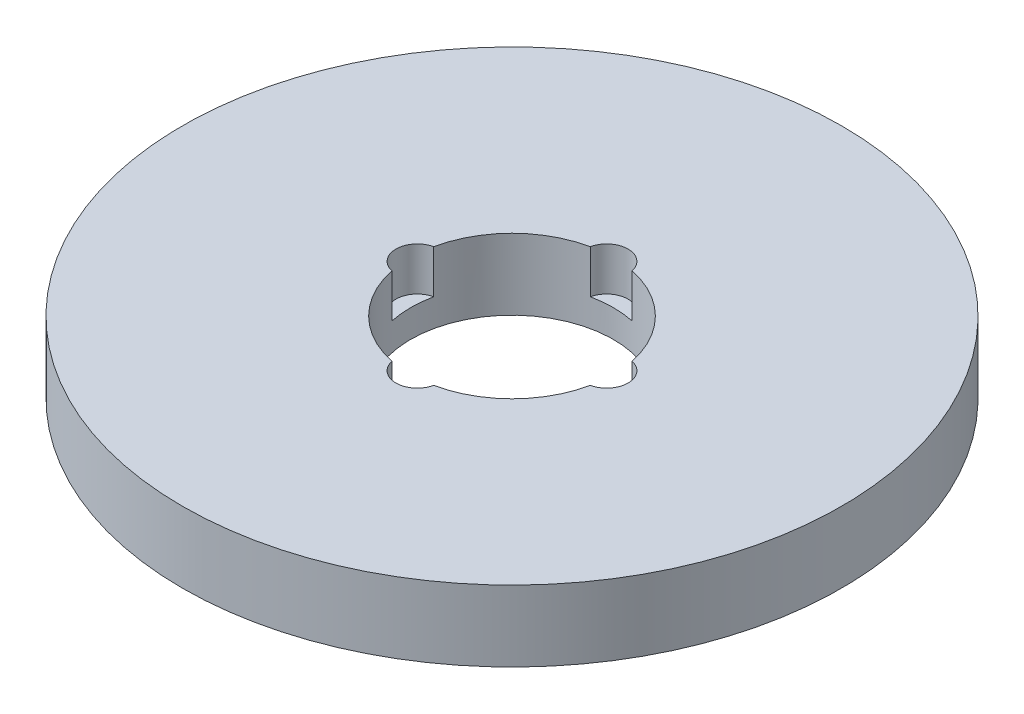
SolidWorks part; units mm, degrees
ref_plane "Front Plane" through (0, 0, 0) normal (0, 0, 1) x (1, 0, 0)
ref_plane "Top Plane" through (0, 0, 0) normal (0, 1, 0) x (1, 0, 0)
ref_plane "Right Plane" through (0, 0, 0) normal (1, 0, 0) x (0, 0, -1)
sketch "Sketch1" plane through (0, 0, 0) normal (0, 1, 0) x (1, 0, 0)
  circle A0 centre (0, 0) radius 32.5
  dimension "FLANGE_OD" = 65
extrude "Boss-Extrude1" add sketch "Sketch1" along normal blind 7
sketch "Sketch2" plane through (0, 0, 0) normal (0, 1, 0) x (1, 0, 0)
  circle A0 centre (0, 0) radius 10
  dimension "BORE_D" = 20
extrude "Cut-Extrude1" cut sketch "Sketch2" along normal through all
sketch "Sketch3" plane through (0, 7, 0) normal (0, 1, 0) x (1, 0, 0)
  circle A0 centre (0, 0) radius 9.3369 construction
  circle A1 centre (-9.3369, 0) radius 2.1095
  dimension "BOLT_D" = 4.2189
  dimension "BOLT_PCD" = 18.6738
extrude "Cut-Extrude2" cut sketch "Sketch3" against normal blind 4.2817
pattern_circular "CirPattern1" count 4 over 360 about axis through (0, 0, 0) along (0, 1, 0) of "Cut-Extrude2"
